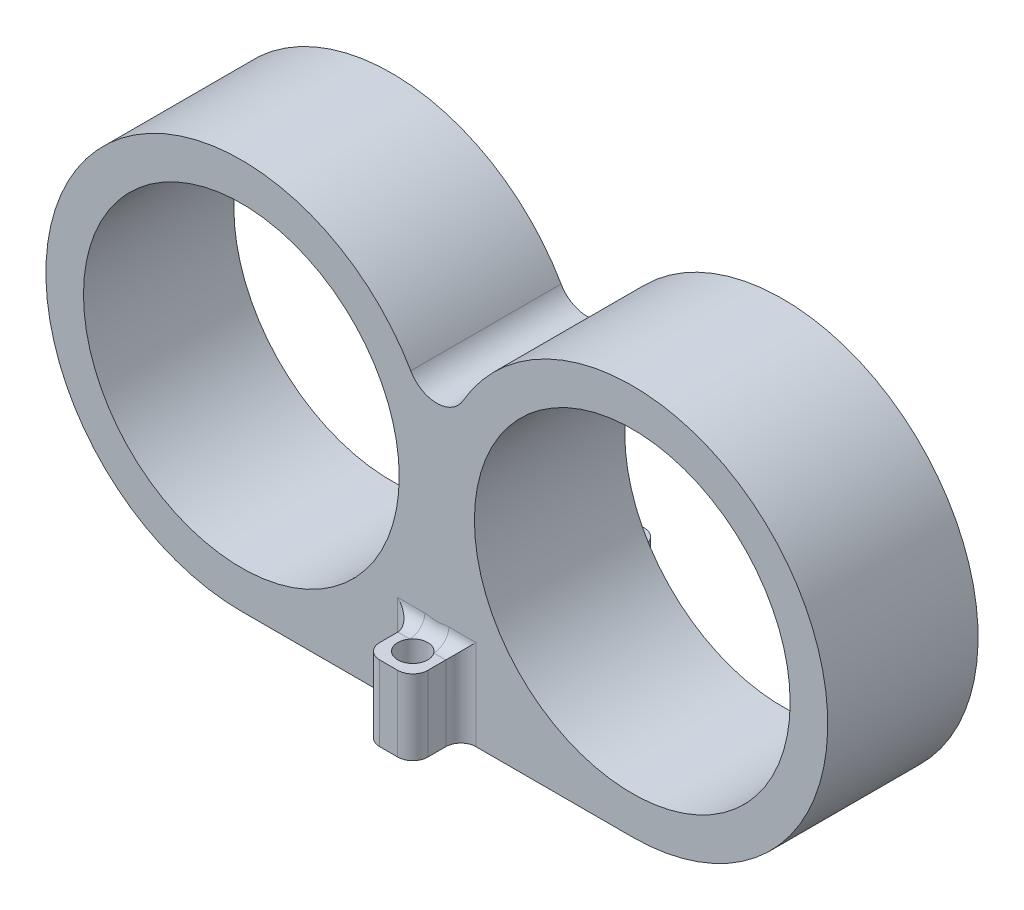
SolidWorks part; units mm, degrees
ref_plane "Front Plane" through (0, 0, 0) normal (0, 0, 1) x (1, 0, 0)
ref_plane "Top Plane" through (0, 0, 0) normal (0, 1, 0) x (1, 0, 0)
ref_plane "Right Plane" through (0, 0, 0) normal (1, 0, 0) x (0, 0, -1)
sketch "Sketch1" plane through (0, 0, 0) normal (0, 0, 1) x (1, 0, 0)
  line L0 (-13, 0) -> (13, 0)
  line L1 (-13, -13) -> (13, -13)
  circle A0 centre (-13, 0) radius 10.5
  circle A1 centre (13, 0) radius 10.5
  circle A2 centre (-13, 0) radius 13
  circle A3 centre (13, 0) radius 13
  dimension "D1" = 21
  dimension "D2" = 21
  dimension "D3" = 26
  dimension "D4" = 13
extrude "Boss-Extrude1" add sketch "Sketch1" along normal blind 10 contours A3 A2 L1 | A2 A0 | A3 A1 region at (-4.0676, -8.9324, 0) region at (13, 12.6323, 0) region at (0, -10.0962, 0)
sketch "Sketch2" plane through (0, -13, 0) normal (0, -1, 0) x (1, 0, 0)
  line L0 (0, -1.5) -> (0, 11.5)
  line L1 (-13, 10) -> (13, 10) construction
  circle A0 centre (0, 11.5) radius 1
  circle A1 centre (0, -1.5) radius 1
  circle A4 centre (0, 11.5) radius 1.75
  circle A5 centre (0, -1.5) radius 1.75
  point P3 (0, 5)
  dimension "D3" = 2
  dimension "D4" = 2
  dimension "D5" = 3.5
  dimension "D6" = 3.5
  dimension "D1" = 13
  dimension "D2" = 5
extrude "Boss-Extrude2" [suppressed] add sketch "Sketch2" against normal blind 6 separate body contours A4 A0 | A5 A1
fillet "Fillet1" radius 2 1 edges at (0, 0, 5)
sketch "Sketch3" plane through (0, 0, 10) normal (0, 0, 1) x (1, 0, 0)
  line L0 (-13, -13) -> (13, -13) construction
  line L1 (-1.6, -13) -> (1.6, -13)
  line L2 (-1.6, -13) -> (-1.6, -8)
  line L3 (-1.6, -8) -> (1.6, -8)
  line L4 (1.6, -13) -> (1.6, -8)
  dimension "D1" = 3.2
  dimension "D2" = 1.6
  dimension "D3" = 5
extrude "Boss-Extrude3" add sketch "Sketch3" along normal blind 3.2
sketch "Sketch4" plane through (0, -8, 0) normal (0, 1, 0) x (1, 0, 0)
  circle A0 centre (0, -11.6) radius 1
  dimension "D1" = 2
extrude "Cut-Extrude1" cut sketch "Sketch4" against normal blind 8.2
ref_plane "Plane1" through (0, 0, 5) normal (0, 0, 1) x (1, 0, 0)
mirror "Mirror1" about plane through (0, 0, 5) normal (0, 0, 1) of "Boss-Extrude3", "Cut-Extrude1"
fillet "Fillet2" radius 1 10 edges at (1.6, -10.5, 10) (0, -8, 10) (-1.6, -10.5, 10) (1.6, -10.5, 13.2) (-1.6, -10.5, 13.2) (1.6, -10.5, 0) (1.6, -10.5, -3.2) (-1.6, -10.5, -3.2) (0, -8, 0) (-1.6, -10.5, 0)
